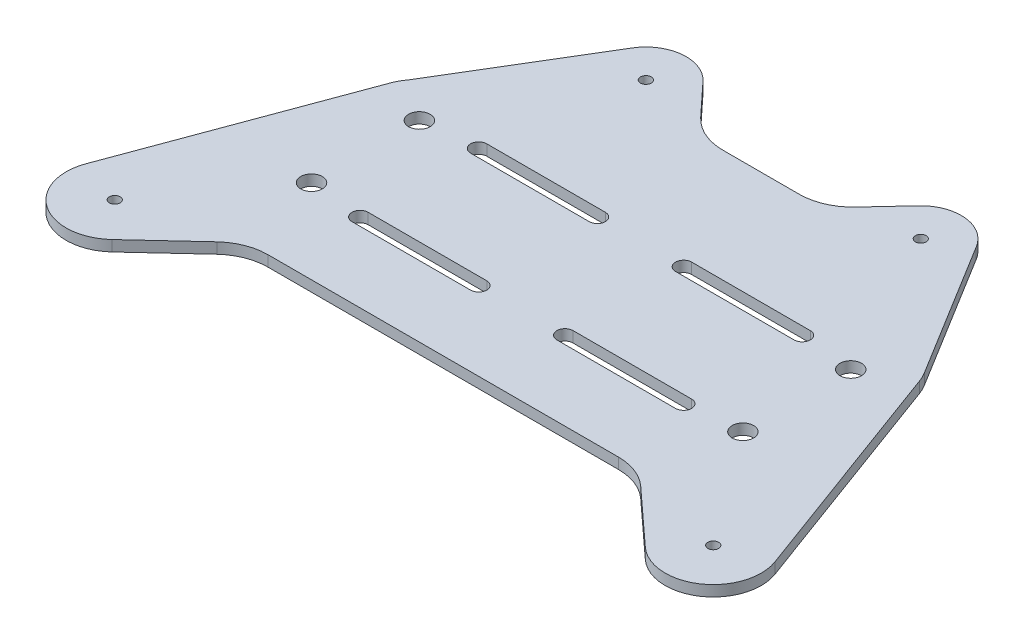
SolidWorks part; units mm, degrees
ref_plane "Front Plane" through (0, 0, 0) normal (0, 0, 1) x (1, 0, 0)
ref_plane "Top Plane" through (0, 0, 0) normal (0, 1, 0) x (1, 0, 0)
ref_plane "Right Plane" through (0, 0, 0) normal (1, 0, 0) x (0, 0, -1)
sketch "Sketch1" plane through (0, 0, 0) normal (0, 1, 0) x (1, 0, 0)
  line L1 (-8.2126, -4.5965) -> (121.7874, -4.5965)
  line L2 (-8.2126, -4.5965) -> (-8.2126, 85.4035)
  line L3 (-8.2126, 85.4035) -> (121.7874, 85.4035)
  line L4 (121.7874, -4.5965) -> (121.7874, 85.4035)
  dimension "D1" = 130
  dimension "D2" = 90
extrude "Boss-Extrude2" add sketch "Sketch1" along normal blind 2
sketch "Sketch2" plane through (0, 2, 0) normal (0, 1, 0) x (1, 0, 0)
  line L0 (121.7874, 85.4035) -> (-8.2126, 85.4035) construction
  line L1 (16.7874, 50.4035) -> (96.7874, 50.4035)
  line L2 (16.7874, 50.4035) -> (16.7874, 30.4035)
  line L3 (16.7874, 30.4035) -> (96.7874, 30.4035)
  line L4 (96.7874, 50.4035) -> (96.7874, 30.4035)
  line L5 (-8.2126, 85.4035) -> (-8.2126, -4.5965) construction
  circle A0 centre (16.7874, 50.4035) radius 2
  circle A1 centre (16.7874, 30.4035) radius 2
  circle A2 centre (96.7874, 50.4035) radius 2
  circle A3 centre (96.7874, 30.4035) radius 2
  point P6 (16.7874, 40.4035)
  point P7 (56.7874, 50.4035)
  dimension "D1" = 20
  dimension "D2" = 80
  dimension "D3" = 45
  dimension "D4" = 65
extrude "Cut-Extrude1" cut sketch "Sketch2" against normal blind 10 contours A0 | A1 | A3 | A2
sketch "Sketch4" plane through (0, 2, 0) normal (0, 1, 0) x (1, 0, 0)
  line L0 (26.7874, 51.4035) -> (48.7874, 51.4035) construction
  line L1 (26.7874, 52.9035) -> (48.7874, 52.9035)
  line L2 (26.7874, 49.9035) -> (48.7874, 49.9035)
  line L3 (26.7874, 29.4035) -> (48.7874, 29.4035) construction
  line L4 (26.7874, 30.9035) -> (48.7874, 30.9035)
  line L5 (26.7874, 27.9035) -> (48.7874, 27.9035)
  line L6 (64.7874, 51.4035) -> (86.7874, 51.4035) construction
  line L7 (64.7874, 52.9035) -> (86.7874, 52.9035)
  line L8 (64.7874, 49.9035) -> (86.7874, 49.9035)
  line L9 (64.7874, 29.4035) -> (86.7874, 29.4035) construction
  line L10 (64.7874, 30.9035) -> (86.7874, 30.9035)
  line L11 (64.7874, 27.9035) -> (86.7874, 27.9035)
  arc A0 (26.7874, 52.9035) -> (26.7874, 49.9035) centre (26.7874, 51.4035) ccw
  arc A1 (48.7874, 49.9035) -> (48.7874, 52.9035) centre (48.7874, 51.4035) ccw
  arc A2 (26.7874, 30.9035) -> (26.7874, 27.9035) centre (26.7874, 29.4035) ccw
  arc A3 (48.7874, 27.9035) -> (48.7874, 30.9035) centre (48.7874, 29.4035) ccw
  arc A4 (64.7874, 52.9035) -> (64.7874, 49.9035) centre (64.7874, 51.4035) ccw
  arc A5 (86.7874, 49.9035) -> (86.7874, 52.9035) centre (86.7874, 51.4035) ccw
  arc A6 (64.7874, 30.9035) -> (64.7874, 27.9035) centre (64.7874, 29.4035) ccw
  arc A7 (86.7874, 27.9035) -> (86.7874, 30.9035) centre (86.7874, 29.4035) ccw
  circle A8 centre (16.7874, 30.4035) radius 2 construction
  circle A10 centre (16.7874, 50.4035) radius 2 construction
  circle A12 centre (96.7874, 30.4035) radius 2 construction
  circle A14 centre (96.7874, 50.4035) radius 2 construction
  point P2 (37.7874, 51.4035)
  point P7 (37.7874, 29.4035)
  point P14 (75.7874, 51.4035)
  point P21 (75.7874, 29.4035)
  dimension "D1" = 1.5
  dimension "D2" = 1.5
  dimension "D3" = 1.5
  dimension "D5" = 1.5
  dimension "D4" = 10
  dimension "D13" = 10
  dimension "D14" = 10
  dimension "D6" = 22
  dimension "D7" = 22
  dimension "D8" = 22
  dimension "D9" = 22
  dimension "D10" = 22
  dimension "D11" = 21
  dimension "D12" = 0
extrude "Cut-Extrude3" cut sketch "Sketch4" against normal blind 10
sketch "Sketch5" plane through (0, 2, 0) normal (0, 1, 0) x (1, 0, 0)
  line L0 (-8.2126, 40.4035) -> (121.7874, 40.4035) construction
  line L1 (-8.2126, 85.4035) -> (-8.2126, -4.5965) construction
  line L2 (121.7874, -4.5965) -> (121.7874, 85.4035) construction
  line L3 (56.7874, 85.4035) -> (56.7874, -4.5965) construction
  line L4 (121.7874, 85.4035) -> (-8.2126, 85.4035) construction
  line L5 (-8.2126, -4.5965) -> (121.7874, -4.5965) construction
  circle A0 centre (1.2874, 9.4035) radius 1
  circle A1 centre (112.2874, 9.4035) radius 1
  circle A2 centre (31.2874, 77.9035) radius 1
  circle A3 centre (82.2874, 77.9035) radius 1
  dimension "D1" = 111
  dimension "D2" = 55.5
  dimension "D3" = 31
  dimension "D4" = 2
  dimension "D5" = 2
  dimension "D6" = 68.5
  dimension "D8" = 51
  dimension "D9" = 25.5
  dimension "D7" = 0
extrude "Cut-Extrude4" cut sketch "Sketch5" against normal blind 10
sketch "Sketch6" plane through (0, 2, 0) normal (0, 1, 0) x (1, 0, 0)
  line L0 (19.7874, 85.4035) -> (-8.3349, 9.4035)
  line L1 (121.7874, 85.4035) -> (-8.2126, 85.4035) construction
  line L2 (68.2134, 73.7782) -> (76.794, 83.0096)
  line L3 (24.8356, 81.7275) -> (8.2428, 54.2044)
  line L4 (93.7874, 85.4035) -> (121.7874, 9.4035)
  line L5 (121.7874, -4.5965) -> (121.7874, 85.4035) construction
  line L6 (7.4251, 2.7878) -> (20.3789, 14.8057)
  line L7 (20.3789, 14.8057) -> (93.196, 14.8057)
  line L8 (93.196, 14.8057) -> (106.2653, 2.8309)
  line L9 (36.7808, 83.0096) -> (45.3615, 73.7782)
  line L10 (45.3615, 73.7782) -> (68.2134, 73.7782)
  line L11 (88.7393, 81.7275) -> (104.6735, 55.8556)
  circle A0 centre (112.2874, 9.4035) radius 1 construction
  circle A1 centre (1.2874, 9.4035) radius 1 construction
  circle A2 centre (1.2874, 9.4035) radius 9.0243
  circle A3 centre (112.2874, 9.4035) radius 8.9143
  circle A4 centre (31.2874, 77.9035) radius 7.5
  circle A5 centre (16.7874, 50.4035) radius 9.3326
  circle A6 centre (96.7874, 50.4035) radius 9.2847
  circle A7 centre (82.2874, 77.9035) radius 7.5
  circle A8 centre (31.2874, 77.9035) radius 1 construction
  circle A9 centre (82.2874, 77.9035) radius 1 construction
  line M25 (-8.2126, 85.4035) -> (-8.2126, -4.5965)
  line M26 (-8.2126, -4.5965) -> (121.7874, -4.5965)
  line M27 (121.7874, -4.5965) -> (121.7874, 85.4035)
  line M28 (121.7874, 85.4035) -> (-8.2126, 85.4035)
  dimension "D5" = 19.0914
  dimension "D1" = 28
  dimension "D2" = 0
  dimension "D3" = 28
  dimension "D4" = 19.0914
  dimension "D6" = 14.0741
  dimension "D7" = 14.0741
extrude "Cut-Extrude5" cut sketch "Sketch6" against normal through all contours L0 M28 M25 | L4 M28 M27 | A3 L8 L7 L6 A2 L0 L4 M25 M26 M27 | A5 L3 A4 L0 M28 | A7 A4 L9 L10 L2 M28 | A7 L11 L4 M28 region at (18.5901, 2, -75.2522) region at (1.1208, 2, -60.1803) region at (56.7874, 2, -80.2462) region at (56.8771, 2, -4.0198) region at (94.7564, 2, -75.7811) region at (112.4541, 2, -60.0701)
fillet "Fillet1" radius 10 6 edges at (104.6735, 1, -55.8556) (8.2428, 1, -54.2044) (45.3615, 1, -73.7782) (68.2134, 1, -73.7782) (93.196, 1, -14.8057) (20.3789, 1, -14.8057)
